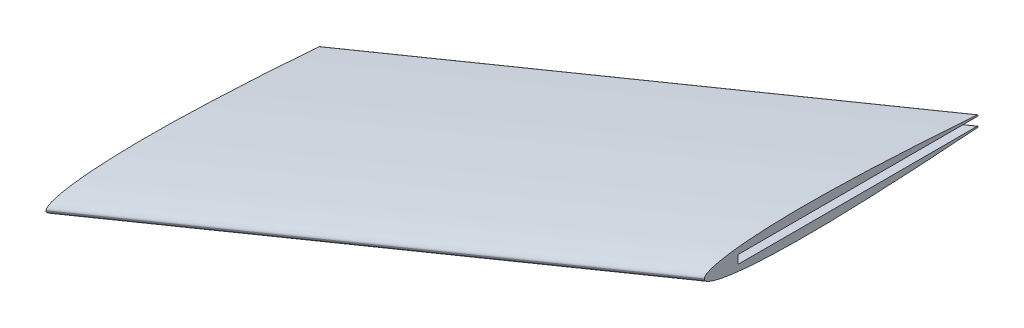
SolidWorks part; units mm, degrees
ref_plane "Front Plane" through (0, 0, 0) normal (0, 0, 1) x (1, 0, 0)
ref_plane "Top Plane" through (0, 0, 0) normal (0, 1, 0) x (1, 0, 0)
ref_plane "Right Plane" through (0, 0, 0) normal (1, 0, 0) x (0, 0, -1)
sketch "Sketch2" plane through (0, 0, 0) normal (1, 0, 0) x (0, 0, -1)
  line L0 (0, 0) -> (254.0007, 0) construction
  spline S0 degree 4 poles (0, 0) (0.0001, 0.0734) (0.0105, 0.1688) (0.0416, 0.2889) (0.1076, 0.4395) (0.175, 0.5575) (0.2746, 0.6943) (0.4232, 0.8566) (0.6418, 1.0489) (0.9884, 1.2926) (1.5795, 1.6197) (2.6705, 2.0778) (4.7457, 2.706) (8.7768, 3.528) (15.0214, 4.2937) (23.1914, 4.8427) (32.7645, 5.1028) (42.7029, 5.0977) (52.6393, 4.8928) (61.3292, 4.5832) (68.7754, 4.2449) (74.9775, 3.9218) (79.9396, 3.6404) (86.1369, 3.2631) (92.3387, 2.8526) (98.5274, 2.4126) (104.7304, 1.9408) (109.6663, 1.5472) (114.0305, 1.1816) (117.6913, 0.8633) (120.8706, 0.5767) (123.1687, 0.3658) (126.214, 0.0771) (128.3939, -0.1348) (132.0486, -0.4985) (134.7001, -0.7765) (137.4864, -1.0708) (138.8199, -1.2204) (139.7263, -1.3194) knots 0 0 0 0 0 0.002066 0.002722 0.003494 0.004655 0.00591 0.007512 0.009724 0.012895 0.017904 0.026634 0.043223 0.074288 0.134449 0.204906 0.275363 0.34582 0.416277 0.486734 0.521962 0.557191 0.592419 0.627648 0.698105 0.733333 0.768562 0.80379 0.839019 0.856633 0.874247 0.891862 0.909476 0.932107 0.954738 0.977369 1 1 1 1 1 construction
  spline S1 degree 4 poles (0, 0) (0.0001, 0.0734) (0.0105, 0.1688) (0.0416, 0.2889) (0.1076, 0.4395) (0.175, 0.5575) (0.2746, 0.6943) (0.4232, 0.8566) (0.6418, 1.0489) (0.9884, 1.2926) (1.5795, 1.6197) (2.6705, 2.0778) (4.7457, 2.706) (8.7768, 3.528) (15.0214, 4.2937) (23.1914, 4.8427) (32.7645, 5.1028) (42.7029, 5.0977) (52.6393, 4.8928) (61.3292, 4.5832) (68.7754, 4.2449) (74.9775, 3.9218) (79.9396, 3.6404) (86.1369, 3.2631) (92.3387, 2.8526) (98.5274, 2.4126) (104.7304, 1.9408) (109.6663, 1.5472) (114.0305, 1.1816) (117.6913, 0.8633) (120.8706, 0.5767) (123.1687, 0.3658) (125.3009, 0.1636) (126.4377, 0.0545) (127, 0) knots 0 0 0 0 0 0.002066 0.002722 0.003494 0.004655 0.00591 0.007512 0.009724 0.012895 0.017904 0.026634 0.043223 0.074288 0.134449 0.204906 0.275363 0.34582 0.416277 0.486734 0.521962 0.557191 0.592419 0.627648 0.698105 0.733333 0.768562 0.80379 0.839019 0.856633 0.874247 0.891862 0.909476 0.909476 0.909476 0.909476 0.909476
  spline S2 degree 4 poles (0, 0) (0.0001, -0.0734) (0.0105, -0.1688) (0.0416, -0.2889) (0.1076, -0.4395) (0.175, -0.5575) (0.2746, -0.6943) (0.4232, -0.8566) (0.6418, -1.0489) (0.9884, -1.2926) (1.5795, -1.6197) (2.6705, -2.0778) (4.7457, -2.706) (8.7768, -3.528) (15.0214, -4.2937) (23.1914, -4.8427) (32.7645, -5.1028) (42.7029, -5.0977) (52.6393, -4.8928) (61.3292, -4.5832) (68.7754, -4.2449) (74.9775, -3.9218) (79.9396, -3.6404) (86.1369, -3.2631) (92.3387, -2.8526) (98.5274, -2.4126) (104.7304, -1.9408) (109.6663, -1.5472) (114.0305, -1.1816) (117.6913, -0.8633) (120.8706, -0.5767) (123.1687, -0.3658) (125.3009, -0.1636) (126.4377, -0.0545) (127, 0) knots 0 0 0 0 0 0.002066 0.002722 0.003494 0.004655 0.00591 0.007512 0.009724 0.012895 0.017904 0.026634 0.043223 0.074288 0.134449 0.204906 0.275363 0.34582 0.416277 0.486734 0.521962 0.557191 0.592419 0.627648 0.698105 0.733333 0.768562 0.80379 0.839019 0.856633 0.874247 0.891862 0.909476 0.909476 0.909476 0.909476 0.909476
ref_plane "Plane1" through (146.05, 0, 0) normal (1, 0, 0) x (0, 0, -1)
sketch "Sketch3" plane through (146.05, 0, 0) normal (1, 0, 0) x (0, 0, -1)
  line L0 (101.6, 0) -> (259.3093, 0) construction
  spline S0 degree 4 poles (101.6, 0) (101.6001, 0.0734) (101.6105, 0.1688) (101.6416, 0.2889) (101.7076, 0.4395) (101.775, 0.5575) (101.8746, 0.6943) (102.0232, 0.8566) (102.2418, 1.0489) (102.5884, 1.2926) (103.1795, 1.6197) (104.2705, 2.0778) (106.3457, 2.706) (110.3768, 3.528) (116.6214, 4.2937) (124.7914, 4.8427) (134.3645, 5.1028) (144.3029, 5.0977) (154.2393, 4.8928) (162.9292, 4.5832) (170.3754, 4.2449) (176.5775, 3.9218) (181.5396, 3.6404) (187.7369, 3.2631) (193.9387, 2.8526) (200.1274, 2.4126) (206.3304, 1.9408) (211.2663, 1.5472) (215.6305, 1.1816) (219.2913, 0.8633) (222.4706, 0.5767) (224.7687, 0.3658) (227.814, 0.0771) (229.9939, -0.1348) (233.6486, -0.4985) (236.3001, -0.7765) (239.0864, -1.0708) (240.4199, -1.2204) (241.3263, -1.3194) knots 0 0 0 0 0 0.002066 0.002722 0.003494 0.004655 0.00591 0.007512 0.009724 0.012895 0.017904 0.026634 0.043223 0.074288 0.134449 0.204906 0.275363 0.34582 0.416277 0.486734 0.521962 0.557191 0.592419 0.627648 0.698105 0.733333 0.768562 0.80379 0.839019 0.856633 0.874247 0.891862 0.909476 0.932107 0.954738 0.977369 1 1 1 1 1 construction
  spline S1 degree 4 poles (101.6, 0) (101.6001, 0.0734) (101.6105, 0.1688) (101.6416, 0.2889) (101.7076, 0.4395) (101.775, 0.5575) (101.8746, 0.6943) (102.0232, 0.8566) (102.2418, 1.0489) (102.5884, 1.2926) (103.1795, 1.6197) (104.2705, 2.0778) (106.3457, 2.706) (110.3768, 3.528) (116.6214, 4.2937) (124.7914, 4.8427) (134.3645, 5.1028) (144.3029, 5.0977) (154.2393, 4.8928) (162.9292, 4.5832) (170.3754, 4.2449) (176.5775, 3.9218) (181.5396, 3.6404) (187.7369, 3.2631) (193.9387, 2.8526) (200.1274, 2.4126) (206.3304, 1.9408) (211.2663, 1.5472) (215.6305, 1.1816) (219.2913, 0.8633) (222.4706, 0.5767) (224.7687, 0.3658) (226.9009, 0.1636) (228.0377, 0.0545) (228.6, 0) knots 0 0 0 0 0 0.002066 0.002722 0.003494 0.004655 0.00591 0.007512 0.009724 0.012895 0.017904 0.026634 0.043223 0.074288 0.134449 0.204906 0.275363 0.34582 0.416277 0.486734 0.521962 0.557191 0.592419 0.627648 0.698105 0.733333 0.768562 0.80379 0.839019 0.856633 0.874247 0.891862 0.909476 0.909476 0.909476 0.909476 0.909476
  spline S2 degree 4 poles (101.6, 0) (101.6001, -0.0734) (101.6105, -0.1688) (101.6416, -0.2889) (101.7076, -0.4395) (101.775, -0.5575) (101.8746, -0.6943) (102.0232, -0.8566) (102.2418, -1.0489) (102.5884, -1.2926) (103.1795, -1.6197) (104.2705, -2.0778) (106.3457, -2.706) (110.3768, -3.528) (116.6214, -4.2937) (124.7914, -4.8427) (134.3645, -5.1028) (144.3029, -5.0977) (154.2393, -4.8928) (162.9292, -4.5832) (170.3754, -4.2449) (176.5775, -3.9218) (181.5396, -3.6404) (187.7369, -3.2631) (193.9387, -2.8526) (200.1274, -2.4126) (206.3304, -1.9408) (211.2663, -1.5472) (215.6305, -1.1816) (219.2913, -0.8633) (222.4706, -0.5767) (224.7687, -0.3658) (226.9009, -0.1636) (228.0377, -0.0545) (228.6, 0) knots 0 0 0 0 0 0.002066 0.002722 0.003494 0.004655 0.00591 0.007512 0.009724 0.012895 0.017904 0.026634 0.043223 0.074288 0.134449 0.204906 0.275363 0.34582 0.416277 0.486734 0.521962 0.557191 0.592419 0.627648 0.698105 0.733333 0.768562 0.80379 0.839019 0.856633 0.874247 0.891862 0.909476 0.909476 0.909476 0.909476 0.909476
loft "Loft1" add profiles "Sketch2", "Sketch3" connector at (0, 0, -127) connector at (146.05, 0, -228.6)
sketch "Shape Of Fins" plane through (0, 0, 0) normal (0, 1, 0) x (1, 0, 0)
  line L0 (0, 12.7) -> (146.05, 114.3)
  line L1 (0, 127) -> (0, 0.0003) construction
  line L2 (146.05, 101.6003) -> (146.05, 228.6) construction
  line L3 (146.05, 114.3) -> (146.05, 215.9)
  line L4 (146.05, 215.9) -> (0, 215.9)
  line L5 (0, 215.9) -> (0, 12.7)
  line L6 (0, 215.9) -> (0, 292.1)
  line L7 (0, 292.1) -> (146.05, 292.1)
  line L8 (146.05, 292.1) -> (146.05, 215.9)
  dimension "D1" = 203.2
  dimension "D2" = 12.7
  dimension "D3" = 101.6
  dimension "D4" = 76.2
extrude "Cut Fin Shape - Bottom (No Midplane)" cut sketch "Shape Of Fins" against normal blind 1.5875 contours L8 L7 L6 L4 | L4 L5 L0 L3 region at (64.9111, 0, -136.8778) region at (73.025, 0, -254)
extrude "Cut Fin Shape - Top (No Midplane)" cut sketch "Shape Of Fins<2>" along normal blind 1.5875 contours L4 L5 L0 L3 | L8 L7 L6 L4 region at (64.9111, 0, -136.8778) region at (73.025, 0, -254)
sketch "Shape Of Fins<2>" plane through (0, 0, 0) normal (0, 1, 0) x (1, 0, 0) same geometry as "Shape Of Fins"
chamfer "Chamfer5" [suppressed] distance 7.62 distance2 8.255
chamfer "Chamfer6" [suppressed] distance 6.35 angle 45
sketch "Sketch10" plane through (0, 0, 0) normal (0, 1, 0) x (1, 0, 0)
  line L0 (0, 12.7) -> (146.05, 114.3)
  line L1 (146.05, 114.3) -> (146.05, 127)
  line L2 (146.05, 114.3) -> (146.05, 215.9) construction
  line L6 (0, 25.4) -> (146.05, 127)
  line L7 (0, 25.4) -> (0, 12.7)
  dimension "D1" = 12.7
  dimension "D2" = 12.7
extrude "Cut For 3D Print Innaccuracy" [suppressed] cut sketch "Sketch10" against normal mid plane 5.08
sketch "Sketch11" plane through (0, 0, 0) normal (1, 0, 0) x (0, 0, -1)
  line L1 (-8.5977, 9.5414) -> (242.836, 9.5414)
  line L2 (-8.5977, 9.5414) -> (-8.5977, -8.9307)
  line L3 (-8.5977, -8.9307) -> (242.836, -8.9307)
  line L4 (242.836, 9.5414) -> (242.836, -8.9307)
fillet "Fillet1" radius 0.254 2 edges
